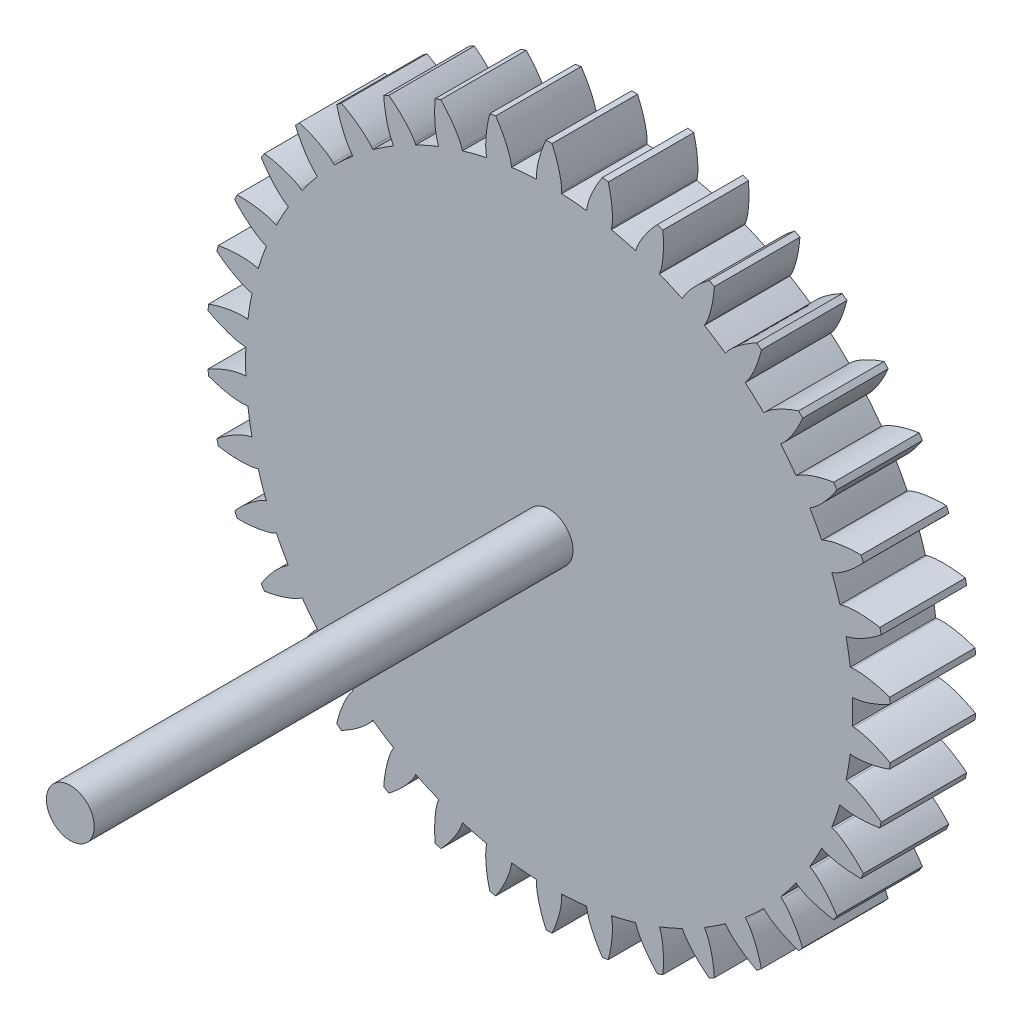
SolidWorks part; units mm, degrees
ref_plane "前视基准面" through (0, 0, 0) normal (0, 0, 1) x (1, 0, 0)
ref_plane "上视基准面" through (0, 0, 0) normal (0, 1, 0) x (1, 0, 0)
ref_plane "右视基准面" through (0, 0, 0) normal (1, 0, 0) x (0, 0, -1)
other "Configuration Table"
sketch "草图1" plane through (0, 0, 0) normal (0, 0, 1) x (1, 0, 0)
  line L0 (0, 0) -> (3, 0) construction
  line L1 (0, 0) -> (2.8978, 0.7765) construction
  line L2 (0, 0) -> (2.7305, 0.701)
  line L3 (2.8978, 0.7765) -> (2.8978, -0.7765) construction
  line L4 (0, 0) -> (2.7305, -0.701)
  circle A0 centre (0, 0) radius 4
  circle A1 centre (0, 0) radius 3 construction
  circle A2 centre (0, 0) radius 1.75
  circle A3 centre (0, 0) radius 2.8191 construction
  circle A4 centre (0, 0) radius 1.4
  spline S0 degree 4 poles (2.7305, 0.701) (2.7514, 0.7063) (2.8083, 0.7255) (2.9105, 0.779) (3.0627, 0.8875) (3.236, 1.0573) (3.4253, 1.3046) (3.6012, 1.6247) (3.742, 2.0003) (3.8364, 2.4221) (3.8779, 2.852) (3.8707, 3.2837) (3.8157, 3.7334) (3.69, 4.2802) (3.4574, 4.9086) (3.0836, 5.5918) (2.5556, 6.2772) (1.9356, 6.8796) (1.2391, 7.3923) (0.4849, 7.8122) (-0.3175, 8.1368) (-1.1468, 8.3674) (-2.0054, 8.5023) (-2.7502, 8.5427) (-3.4127, 8.5171) (-3.8849, 8.4708) (-4.3024, 8.4076) (-4.5772, 8.3558) (-4.9624, 8.2714) (-5.2496, 8.1908) (-5.5362, 8.1071) (-5.6783, 8.056) (-5.7704, 8.0254) knots 0 0 0 0 0 0.005604 0.015718 0.02996 0.048734 0.068727 0.096889 0.125051 0.153212 0.181374 0.209535 0.237696 0.271429 0.327752 0.384075 0.440398 0.496721 0.553044 0.609367 0.66569 0.722013 0.778336 0.834659 0.86282 0.890982 0.909091 0.931818 0.954545 0.977273 1 1 1 1 1 construction
  spline S1 degree 4 poles (2.7305, 0.701) (2.7514, 0.7063) (2.8083, 0.7255) (2.9105, 0.779) (3.0627, 0.8875) (3.236, 1.0573) (3.4253, 1.3046) (3.6012, 1.6247) (3.742, 2.0003) (3.8364, 2.4221) (3.8779, 2.852) (3.8707, 3.2837) (3.8157, 3.7334) (3.69, 4.2802) (3.4574, 4.9086) (3.0836, 5.5918) (2.5556, 6.2772) (1.9356, 6.8796) (1.2391, 7.3923) (0.4849, 7.8122) (-0.3175, 8.1368) (-1.1468, 8.3674) (-2.0054, 8.5023) (-2.7502, 8.5427) (-3.4127, 8.5171) (-3.8849, 8.4708) (-4.2047, 8.4224) (-4.3632, 8.395) (-4.4251, 8.3835) knots 0 0 0 0 0 0.005604 0.015718 0.02996 0.048734 0.068727 0.096889 0.125051 0.153212 0.181374 0.209535 0.237696 0.271429 0.327752 0.384075 0.440398 0.496721 0.553044 0.609367 0.66569 0.722013 0.778336 0.834659 0.86282 0.890982 0.909091 0.909091 0.909091 0.909091 0.909091
  spline S2 degree 4 poles (2.7305, -0.701) (2.7514, -0.7063) (2.8083, -0.7255) (2.9105, -0.779) (3.0627, -0.8875) (3.236, -1.0573) (3.4253, -1.3046) (3.6012, -1.6247) (3.742, -2.0003) (3.8364, -2.4221) (3.8779, -2.852) (3.8707, -3.2837) (3.8157, -3.7334) (3.69, -4.2802) (3.4574, -4.9086) (3.0836, -5.5918) (2.5556, -6.2772) (1.9356, -6.8796) (1.2391, -7.3923) (0.4849, -7.8122) (-0.3175, -8.1368) (-1.1468, -8.3674) (-2.0054, -8.5023) (-2.7502, -8.5427) (-3.4127, -8.5171) (-3.8849, -8.4708) (-4.3024, -8.4076) (-4.5772, -8.3558) (-4.9624, -8.2714) (-5.2496, -8.1908) (-5.5362, -8.1071) (-5.6783, -8.056) (-5.7704, -8.0254) knots 0 0 0 0 0 0.005604 0.015718 0.02996 0.048734 0.068727 0.096889 0.125051 0.153212 0.181374 0.209535 0.237696 0.271429 0.327752 0.384075 0.440398 0.496721 0.553044 0.609367 0.66569 0.722013 0.778336 0.834659 0.86282 0.890982 0.909091 0.931818 0.954545 0.977273 1 1 1 1 1 construction
  spline S3 degree 4 poles (2.7305, -0.701) (2.7514, -0.7063) (2.8083, -0.7255) (2.9105, -0.779) (3.0627, -0.8875) (3.236, -1.0573) (3.4253, -1.3046) (3.6012, -1.6247) (3.742, -2.0003) (3.8364, -2.4221) (3.8779, -2.852) (3.8707, -3.2837) (3.8157, -3.7334) (3.69, -4.2802) (3.4574, -4.9086) (3.0836, -5.5918) (2.5556, -6.2772) (1.9356, -6.8796) (1.2391, -7.3923) (0.4849, -7.8122) (-0.3175, -8.1368) (-1.1468, -8.3674) (-2.0054, -8.5023) (-2.7502, -8.5427) (-3.4127, -8.5171) (-3.8849, -8.4708) (-4.2047, -8.4224) (-4.3632, -8.395) (-4.4251, -8.3835) knots 0 0 0 0 0 0.005604 0.015718 0.02996 0.048734 0.068727 0.096889 0.125051 0.153212 0.181374 0.209535 0.237696 0.271429 0.327752 0.384075 0.440398 0.496721 0.553044 0.609367 0.66569 0.722013 0.778336 0.834659 0.86282 0.890982 0.909091 0.909091 0.909091 0.909091 0.909091
  point P15 (2.8978, 0)
  dimension "齿顶圆直径" = 8
  dimension "分度圆直径" = 6
  dimension "齿根圆直径" = 3.5
  dimension "基圆直径" = 5.6382
  dimension "内孔直径" = 2.8
  dimension "渐近线镜像线夹角" = 15
extrude "凸台-拉伸1" add sketch "草图1" along normal blind 5 contours A0 | A4
extrude "切除-拉伸1" cut sketch "草图1<3>" along normal through all contours A2 S3 A0 S1 region at (3.0753, 0, 0)
sketch "草图1<3>" plane through (0, 0, 0) normal (0, 0, 1) x (1, 0, 0) same geometry as "草图1"
pattern_circular "阵列(圆周)1" count 6 every 60 about axis through (0, 0, 5) along (0, 0, 1) of "切除-拉伸1"
sketch "草图2" plane through (0, 0, 5) normal (0, 0, 1) x (1, 0, 0)
  line L0 (0, 0) -> (19, 0) construction
  line L1 (0, 0) -> (17.8389, 0.7378)
  line L2 (0, 0) -> (17.8389, -0.7378)
  line L3 (17.8389, 0.7378) -> (17.8389, -0.7378) construction
  circle A0 centre (0, 0) radius 19 construction
  circle A1 centre (0, 0) radius 17.8542 construction
  circle A2 centre (0, 0) radius 17.75
  circle A3 centre (0, 0) radius 20
  circle A4 centre (0, 0) radius 1.4
  spline S0 degree 4 poles (17.8389, -0.7378) (17.8728, -0.7392) (17.9406, -0.7441) (18.0752, -0.7621) (18.3288, -0.8123) (18.6635, -0.9051) (19.1205, -1.0702) (19.658, -1.3153) (20.4669, -1.7609) (21.5195, -2.5027) (22.8507, -3.7145) (24.3091, -5.5094) (25.6114, -7.6908) (26.6766, -10.2121) (27.4216, -12.8444) (27.8645, -15.543) (28.0306, -18.4074) (27.8656, -21.9567) (27.1273, -26.1356) (25.5694, -30.8158) (23.0564, -35.6845) (20.2692, -39.5823) (17.5235, -42.6283) (15.0272, -44.9572) (12.9164, -46.6904) (10.7035, -48.2904) (8.3975, -49.7545) (5.4145, -51.4121) (1.6874, -53.1227) (-2.8247, -54.7082) (-7.1558, -55.7237) (-10.5228, -56.2445) (-12.9095, -56.489) (-14.244, -56.5948) (-15.5428, -56.66) (-16.5612, -56.6949) (-17.638, -56.7056) (-18.2041, -56.705) (-18.894, -56.6964) (-19.4423, -56.6837) (-20.126, -56.6612) (-20.9547, -56.6234) (-21.9141, -56.5638) (-23.0135, -56.4746) (-24.1084, -56.3645) (-25.2027, -56.2336) (-26.0203, -56.1199) (-26.5651, -56.0373) (-26.8369, -55.9943) knots 0 0 0 0 0 0.001401 0.002802 0.005604 0.010661 0.015718 0.022839 0.02996 0.048734 0.068727 0.096889 0.125051 0.153212 0.181374 0.209535 0.237696 0.271429 0.327752 0.384075 0.440398 0.496721 0.524883 0.553044 0.581206 0.609367 0.637529 0.66569 0.722013 0.778336 0.834659 0.84874 0.86282 0.876901 0.890982 0.900036 0.909091 0.914773 0.920455 0.926136 0.931818 0.943182 0.954545 0.965909 0.977273 0.988636 1 1 1 1 1 construction
  spline S1 degree 4 poles (17.8389, -0.7378) (17.8728, -0.7392) (17.9406, -0.7441) (18.0752, -0.7621) (18.3288, -0.8123) (18.6635, -0.9051) (19.1205, -1.0702) (19.658, -1.3153) (20.4669, -1.7609) (21.5195, -2.5027) (22.8507, -3.7145) (24.3091, -5.5094) (25.6114, -7.6908) (26.6766, -10.2121) (27.4216, -12.8444) (27.8645, -15.543) (28.0306, -18.4074) (27.8656, -21.9567) (27.1273, -26.1356) (25.5694, -30.8158) (23.0564, -35.6845) (20.2692, -39.5823) (17.5235, -42.6283) (15.0272, -44.9572) (12.9164, -46.6904) (10.7035, -48.2904) (8.3975, -49.7545) (5.4145, -51.4121) (1.6874, -53.1227) (-2.8247, -54.7082) (-7.1558, -55.7237) (-10.5228, -56.2445) (-12.9095, -56.489) (-14.244, -56.5948) (-15.5428, -56.66) (-16.5612, -56.6949) (-17.4764, -56.704) (-17.8641, -56.7049) (-18.0636, -56.7042) knots 0 0 0 0 0 0.001401 0.002802 0.005604 0.010661 0.015718 0.022839 0.02996 0.048734 0.068727 0.096889 0.125051 0.153212 0.181374 0.209535 0.237696 0.271429 0.327752 0.384075 0.440398 0.496721 0.524883 0.553044 0.581206 0.609367 0.637529 0.66569 0.722013 0.778336 0.834659 0.84874 0.86282 0.876901 0.890982 0.900036 0.909091 0.909091 0.909091 0.909091 0.909091
  spline S2 degree 4 poles (17.8389, 0.7378) (17.8728, 0.7392) (17.9406, 0.7441) (18.0752, 0.7621) (18.3288, 0.8123) (18.6635, 0.9051) (19.1205, 1.0702) (19.658, 1.3153) (20.4669, 1.7609) (21.5195, 2.5027) (22.8507, 3.7145) (24.3091, 5.5094) (25.6114, 7.6908) (26.6766, 10.2121) (27.4216, 12.8444) (27.8645, 15.543) (28.0306, 18.4074) (27.8656, 21.9567) (27.1273, 26.1356) (25.5694, 30.8158) (23.0564, 35.6845) (20.2692, 39.5823) (17.5235, 42.6283) (15.0272, 44.9572) (12.9164, 46.6904) (10.7035, 48.2904) (8.3975, 49.7545) (5.4145, 51.4121) (1.6874, 53.1227) (-2.8247, 54.7082) (-7.1558, 55.7237) (-10.5228, 56.2445) (-12.9095, 56.489) (-14.244, 56.5948) (-15.5428, 56.66) (-16.5612, 56.6949) (-17.638, 56.7056) (-18.2041, 56.705) (-18.894, 56.6964) (-19.4423, 56.6837) (-20.126, 56.6612) (-20.9547, 56.6234) (-21.9141, 56.5638) (-23.0135, 56.4746) (-24.1084, 56.3645) (-25.2027, 56.2336) (-26.0203, 56.1199) (-26.5651, 56.0373) (-26.8369, 55.9943) knots 0 0 0 0 0 0.001401 0.002802 0.005604 0.010661 0.015718 0.022839 0.02996 0.048734 0.068727 0.096889 0.125051 0.153212 0.181374 0.209535 0.237696 0.271429 0.327752 0.384075 0.440398 0.496721 0.524883 0.553044 0.581206 0.609367 0.637529 0.66569 0.722013 0.778336 0.834659 0.84874 0.86282 0.876901 0.890982 0.900036 0.909091 0.914773 0.920455 0.926136 0.931818 0.943182 0.954545 0.965909 0.977273 0.988636 1 1 1 1 1 construction
  spline S3 degree 4 poles (17.8389, 0.7378) (17.8728, 0.7392) (17.9406, 0.7441) (18.0752, 0.7621) (18.3288, 0.8123) (18.6635, 0.9051) (19.1205, 1.0702) (19.658, 1.3153) (20.4669, 1.7609) (21.5195, 2.5027) (22.8507, 3.7145) (24.3091, 5.5094) (25.6114, 7.6908) (26.6766, 10.2121) (27.4216, 12.8444) (27.8645, 15.543) (28.0306, 18.4074) (27.8656, 21.9567) (27.1273, 26.1356) (25.5694, 30.8158) (23.0564, 35.6845) (20.2692, 39.5823) (17.5235, 42.6283) (15.0272, 44.9572) (12.9164, 46.6904) (10.7035, 48.2904) (8.3975, 49.7545) (5.4145, 51.4121) (1.6874, 53.1227) (-2.8247, 54.7082) (-7.1558, 55.7237) (-10.5228, 56.2445) (-12.9095, 56.489) (-14.244, 56.5948) (-15.5428, 56.66) (-16.5612, 56.6949) (-17.4764, 56.704) (-17.8641, 56.7049) (-18.0636, 56.7042) knots 0 0 0 0 0 0.001401 0.002802 0.005604 0.010661 0.015718 0.022839 0.02996 0.048734 0.068727 0.096889 0.125051 0.153212 0.181374 0.209535 0.237696 0.271429 0.327752 0.384075 0.440398 0.496721 0.524883 0.553044 0.581206 0.609367 0.637529 0.66569 0.722013 0.778336 0.834659 0.84874 0.86282 0.876901 0.890982 0.900036 0.909091 0.909091 0.909091 0.909091 0.909091
  point P16 (17.8389, 0)
  dimension "内孔直径" = 2.8
  dimension "分度圆直径" = 38
  dimension "齿顶圆直径" = 40
  dimension "基圆直径" = 35.7083
  dimension "齿根圆直径" = 35.5
  dimension "渐开线镜像线夹角" = 2.368
extrude "凸台-拉伸2" add sketch "草图2" along normal blind 5 contours A3 | A4
extrude "切除-拉伸3" cut sketch "草图2<3>" along normal through all contours S3 L1 A2 L2 S1 A3 region at (19.0065, 0, 5)
sketch "草图2<3>" plane through (0, 0, 5) normal (0, 0, 1) x (1, 0, 0) same geometry as "草图2"
pattern_circular "阵列(圆周)2" count 38 over 360 about axis through (0, 0, 10) along (0, 0, 1) of "切除-拉伸3"
sketch "草图3" plane through (0, 0, 10) normal (0, 0, 1) x (1, 0, 0)
  circle A0 centre (0, 0) radius 1.4
  circle A1 centre (0, 0) radius 1.4 construction
extrude "凸台-拉伸3" add sketch "草图3" along normal blind 28 separate body
extrude "凸台-拉伸4" add sketch "草图3<2>" against normal blind 15
sketch "草图3<2>" plane through (0, 0, 10) normal (0, 0, 1) x (1, 0, 0) same geometry as "草图3"
equation "\"m\"= 1'模数"
equation "\"z\"= 6'齿数"
equation "\"a\"= 20度'压力角"
equation "\"d\"= \"m\" * \"z\"'分度圆直径"
equation "\"da\"= ( \"z\" + 2 ) * \"m\"'齿顶圆直径"
equation "\"df\"= ( \"z\" - 2.5 ) * \"m\"'齿根圆直径"
equation "\"s\"= 0.5 * PI * \"m\"'分度圆齿厚"
equation "\"r\"= 0.38 * \"m\"'齿根圆角"
equation "\"B\"= 0.3 * \"d\"'齿厚"
equation "\"db\"= \"m\" * \"z\" * cos ( \"a\" )'基圆直径"
equation "\"rb\"= \"db\" / 2'基圆半径"
equation "\"齿顶圆直径@草图1\"= \"da\""
equation "\"分度圆直径@草图1\"= \"d\""
equation "\"齿根圆直径@草图1\"= \"df\""
equation "\"基圆直径@草图1\"= \"db\""
equation "\"渐近线镜像线夹角@草图1\"= 360 / 4 / \"z\""
equation "\"h\"= 5'齿轮厚度"
equation "\"ir\"= 2.8'内孔直径"
equation "\"内孔直径@草图1\"= \"ir\""
equation "\"齿轮厚@凸台-拉伸1\"= \"h\""
equation "\"齿轮夹角@阵列(圆周)1\"= 360 / \"z\""
equation "\"齿数@阵列(圆周)1\"= \"z\""
equation "\"m1\"= 1'模数"
equation "\"z1\"= 38'齿数"
equation "\"a1\"= 20度'压力角"
equation "\"d1\"= \"m1\" * \"z1\"'分度圆直径"
equation "\"da1\"= ( \"z1\" + 2 ) * \"m1\"'齿顶圆直径"
equation "\"df1\"= ( \"z1\" - 2.5 ) * \"m1\"'齿根圆直径"
equation "\"s1\"= 0.5 * PI * \"m1\"'分度圆齿厚"
equation "\"r1\"= 0.38 * \"m1\"'齿根圆角"
equation "\"B1\"= 0.3 * \"d1\"'齿厚"
equation "\"db1\"= \"m1\" * \"z1\" * cos ( \"a1\" )'基圆直径"
equation "\"rb1\"= \"db1\" / 2'基圆半径"
equation "\"分度圆直径@草图2\"= \"d1\""
equation "\"齿顶圆直径@草图2\"= \"da1\""
equation "\"基圆直径@草图2\"= \"db1\""
equation "\"齿根圆直径@草图2\"= \"df1\""
equation "\"渐开线镜像线夹角@草图2\"= 360 / 4 / \"z1\""
equation "\"内孔直径@草图2\"= \"ir\""
equation "\"二层齿轮厚@凸台-拉伸2\" = \"h1\""
equation "\"h1\"= 5'齿轮厚度"
equation "\"二层齿数@阵列(圆周)2\"= \"z1\""
